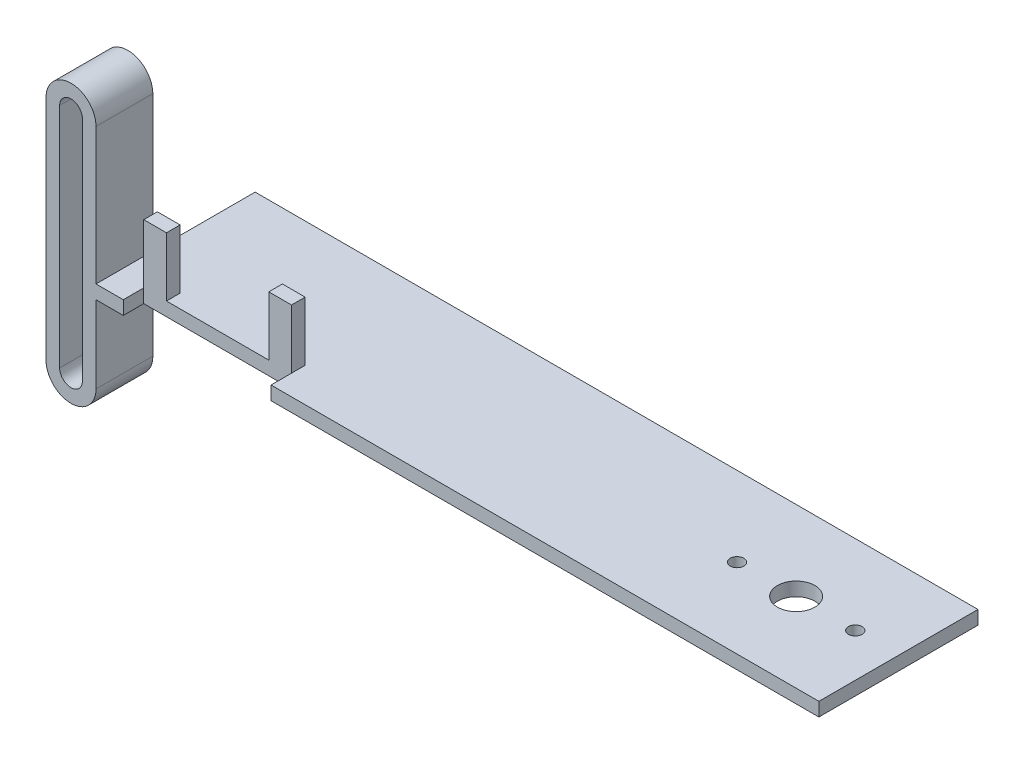
SolidWorks part; units mm, degrees
ref_plane "Front Plane" through (0, 0, 0) normal (0, 0, 1) x (1, 0, 0)
ref_plane "Top Plane" through (0, 0, 0) normal (0, 1, 0) x (1, 0, 0)
ref_plane "Right Plane" through (0, 0, 0) normal (1, 0, 0) x (0, 0, -1)
sketch "Sketch1" plane through (0, 0, 0) normal (0, 1, 0) x (1, 0, 0)
  line L0 (47.5, 13.6856) -> (47.5, -3.2344) construction
  line L1 (-100, 22.5) -> (70, 22.5)
  line L2 (-100, 22.5) -> (-100, -12.5)
  line L3 (-100, -12.5) -> (70, -12.5)
  line L4 (70, 22.5) -> (70, -12.5)
  circle A4 centre (47.5, 5) radius 4.125
  circle A5 centre (60.5, 5) radius 1.5
  circle A6 centre (34.5, 5) radius 1.5
  point P0 (0, 0)
  point P17 (70, 5)
  dimension "D3" = 22.5
  dimension "D4" = 8.25
  dimension "D5" = 3
  dimension "D1" = 35
  dimension "D2" = 170
  dimension "D6" = 13
extrude "Boss-Extrude1" add sketch "Sketch1" along normal blind 3 contours L3 L4 L1 L2 A4 | L3 region at (-15.7182, 0, -5)
sketch "Sketch2" plane through (0, 0, 0) normal (0, 0, 1) x (1, 0, 0)
  line L0 (-94.5, 33) -> (-94.5, -17) construction
  line L1 (-92, 33) -> (-92, -17)
  line L2 (-97, 33) -> (-97, -17)
  line L3 (-89, 33) -> (-89, -17)
  line L4 (-100, 33) -> (-100, -17)
  line L7 (-83, 6.4998) -> (-50.5, 6.4998)
  line L8 (-83, 6.4998) -> (-83, -3.3981)
  line L9 (-83, -3.3981) -> (-50.5, -3.3981)
  line L10 (-50.5, 6.4998) -> (-50.5, -3.3981)
  arc A0 (-92, 33) -> (-97, 33) centre (-94.5, 33) ccw
  arc A1 (-97, -17) -> (-92, -17) centre (-94.5, -17) ccw
  arc A2 (-100, -17) -> (-89, -17) centre (-94.5, -17) ccw
  arc A3 (-89, 33) -> (-100, 33) centre (-94.5, 33) ccw
  point P2 (-94.5, 8)
  dimension "D4" = 5.5
  dimension "D1" = 3
  dimension "D2" = 3
  dimension "D3" = 5
  dimension "D5" = 50
  dimension "D6" = 50
  dimension "D7" = 6
  dimension "D8" = 32.5
extrude "Boss-Extrude2" add sketch "Sketch2" along normal up to surface (12.5 mm away) contours L3 A3 L4 A2 A1 L2 A0 L1 region at (-89.6198, 8, 0) up to face at (-15, 1.5, 12.5)
extrude "Cut-Extrude1" cut sketch "Sketch2<2>" against normal through all both and the other way through all contours L2 A1 L1 A0 region at (-94.5, 8, 0)
sketch "Sketch2<2>" plane through (0, 0, 0) normal (0, 0, 1) x (1, 0, 0) same geometry as "Sketch2"
extrude "Cut-Extrude2" cut sketch "Sketch2<3>" against normal up to surface (22.5 mm away) contours L3 A3 L4 A2 A1 L2 A0 L1 region at (-89.6198, 8, 0) up to face at (-11, 1.5, -22.5)
sketch "Sketch2<3>" plane through (0, 0, 0) normal (0, 0, 1) x (1, 0, 0) same geometry as "Sketch2"
extrude "Cut-Extrude3" cut sketch "Sketch2<5>" along normal up to surface (12.5 mm away) from offset 8 contours L10 L7 L8 L9 region at (-66.75, 1.5509, 0) up to face at (-94.5, 8, 12.5)
sketch "Sketch2<5>" plane through (0, 0, 0) normal (0, 0, 1) x (1, 0, 0) same geometry as "Sketch2"
sketch "Sketch4" plane through (0, 0, 8) normal (0, 0, 1) x (1, 0, 0)
  line L1 (-83, 3) -> (-78, 3)
  line L2 (-83, 3) -> (-83, 16)
  line L3 (-83, 16) -> (-78, 16)
  line L4 (-78, 3) -> (-78, 16)
  line L5 (-50.5, 3) -> (-55.5, 3)
  line L6 (-50.5, 3) -> (-50.5, 16)
  line L7 (-50.5, 16) -> (-55.5, 16)
  line L8 (-55.5, 3) -> (-55.5, 16)
extrude "Boss-Extrude3" add sketch "Sketch4" against normal blind 3
